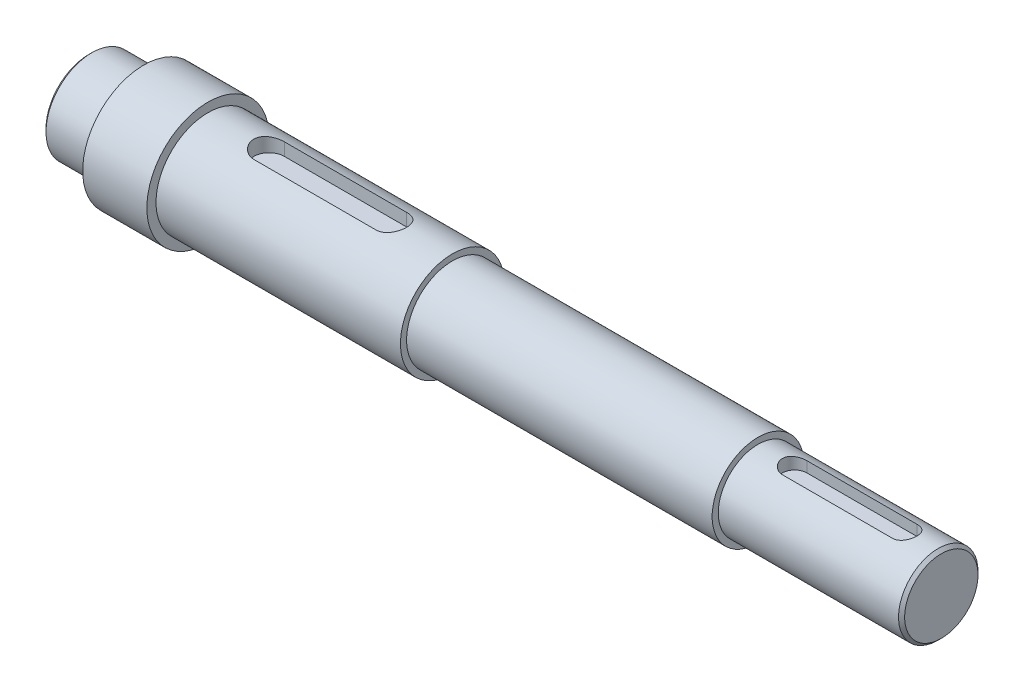
SolidWorks part; units mm, degrees
ref_plane "Front Plane" through (0, 0, 0) normal (0, 0, 1) x (1, 0, 0)
ref_plane "Top Plane" through (0, 0, 0) normal (0, 1, 0) x (1, 0, 0)
ref_plane "Right Plane" through (0, 0, 0) normal (1, 0, 0) x (0, 0, -1)
sketch "Sketch1" plane through (0, 0, 0) normal (1, 0, 0) x (0, 0, -1)
  circle A0 centre (0, 0) radius 17
  dimension "D1" = 34
extrude "Boss-Extrude1" add sketch "Sketch1" along normal blind 40 and the other way blind 40
ref_plane "Plane1" through (0, 17, 0) normal (0, 1, 0) x (1, 0, 0)
sketch "Sketch2" plane through (0, 17, 0) normal (0, 1, 0) x (1, 0, 0)
  line L0 (-20, 0) -> (20, 0) construction
  line L1 (-20, 5) -> (20, 5)
  line L2 (-20, -5) -> (20, -5)
  arc A0 (-20, 5) -> (-20, -5) centre (-20, 0) ccw
  arc A1 (20, -5) -> (20, 5) centre (20, 0) ccw
  point P2 (0, 0)
  dimension "D1" = 10
  dimension "D2" = 40
extrude "Cut-Extrude1" cut sketch "Sketch2" against normal blind 4.9
sketch "Sketch3" plane through (-40, 0, 0) normal (-1, 0, 0) x (0, 0, 1)
  circle A0 centre (0, 0) radius 20
  dimension "D1" = 40
extrude "Boss-Extrude2" add sketch "Sketch3" along normal blind 21
sketch "Sketch4" plane through (-61, 0, 0) normal (-1, 0, 0) x (0, 0, 1)
  circle A0 centre (0, 0) radius 15
  dimension "D1" = 30
extrude "Boss-Extrude3" add sketch "Sketch4" along normal blind 18
chamfer "Chamfer1" distance 1 angle 45 1 edges at (-79, 0, 15)
sketch "Sketch5" plane through (40, 0, 0) normal (1, 0, 0) x (0, 0, -1)
  circle A0 centre (0, 0) radius 15
  dimension "D1" = 30
extrude "Boss-Extrude4" add sketch "Sketch5" along normal blind 100
sketch "Sketch6" plane through (140, 0, 0) normal (1, 0, 0) x (0, 0, -1)
  circle A0 centre (0, 0) radius 13
  dimension "D1" = 26
extrude "Boss-Extrude5" add sketch "Sketch6" along normal blind 60
ref_plane "Plane2" through (0, 13, 0) normal (0, 1, 0) x (1, 0, 0)
sketch "Sketch7" plane through (0, 13, 0) normal (0, 1, 0) x (1, 0, 0)
  line L0 (170, 44.9376) -> (170, -40.9493) construction
  line L1 (140, -15) -> (140, 15) construction
  line L2 (200, -13) -> (200, 13) construction
  line L3 (152, 0) -> (188, 0) construction
  line L4 (152, 4) -> (188, 4)
  line L5 (152, -4) -> (188, -4)
  arc A0 (152, 4) -> (152, -4) centre (152, 0) ccw
  arc A1 (188, -4) -> (188, 4) centre (188, 0) ccw
  point P8 (170, 0)
  dimension "D1" = 8
  dimension "D2" = 36
extrude "Cut-Extrude2" cut sketch "Sketch7" against normal blind 4.1
chamfer "Chamfer2" distance 1 angle 45 1 edges at (200, 0, -13)
